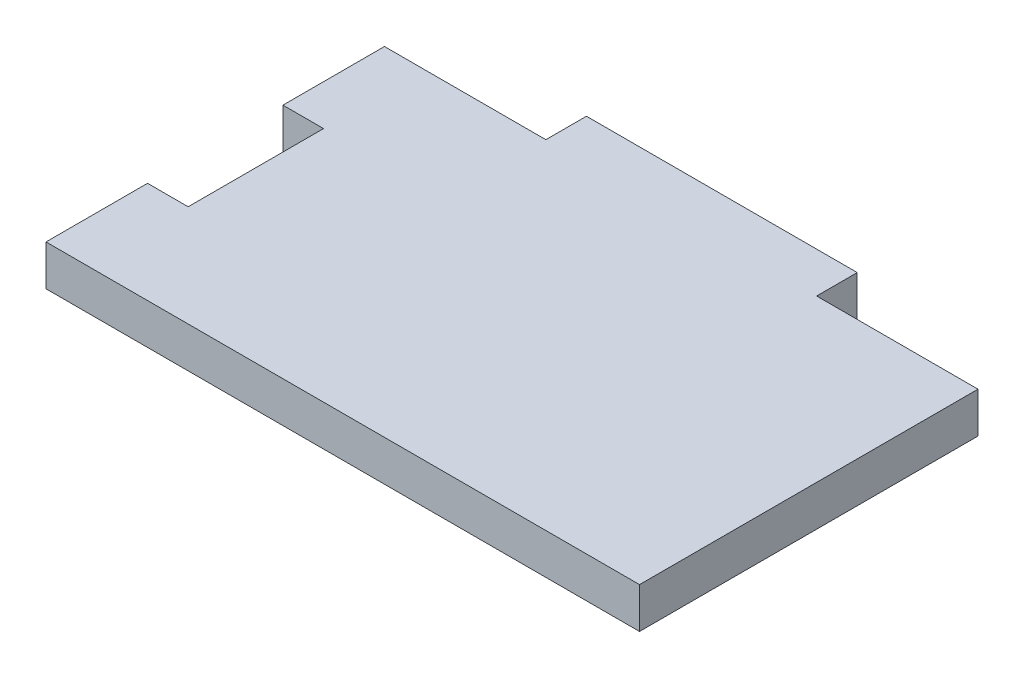
SolidWorks part; units mm, degrees
ref_plane "Front Plane" through (0, 0, 0) normal (0, 0, 1) x (1, 0, 0)
ref_plane "Top Plane" through (0, 0, 0) normal (0, 1, 0) x (1, 0, 0)
ref_plane "Right Plane" through (0, 0, 0) normal (1, 0, 0) x (0, 0, -1)
sketch "Sketch1" plane through (0, 0, 0) normal (0, 0, 1) x (1, 0, 0)
  line L1 (-54.8559, -41.0083) -> (32.8193, -41.0083)
  line L2 (-54.8559, -41.0083) -> (-54.8559, -35.0083)
  line L3 (-54.8559, -35.0083) -> (32.8193, -35.0083)
  line L4 (32.8193, -41.0083) -> (32.8193, -35.0083)
  line L5 (-31.0183, -35.0083) -> (-31.0183, -41.0083)
  line L6 (8.9817, -35.0083) -> (8.9817, -41.0083)
  point P5 (0, 0)
  point P6 (0, 0)
  point P15 (0, 0)
  point P16 (0, 0)
  dimension "D1" = 87.6752
  dimension "D2" = 6
extrude "Boss-Extrude1" add sketch "Sketch1" along normal blind 50 contours L5 L3 L2 L1 | L6 L3 L5 L1 | L3 L6 L1 L4 region at (-42.9371, -38.0083, 0) region at (-11.0183, -38.0083, 0) region at (20.9005, -38.0083, 0)
extrude "Boss-Extrude2" add sketch "Sketch1<3>" against normal blind 6 contours L6 L3 L5 L1 region at (-11.0183, -38.0083, 0)
sketch "Sketch1<3>" plane through (0, 0, 0) normal (0, 0, 1) x (1, 0, 0) same geometry as "Sketch1"
sketch "Sketch2" plane through (0, -35.0083, 0) normal (0, 1, 0) x (1, 0, 0)
  line L0 (-54.8559, -50) -> (-54.8559, 0) construction
  line L1 (-54.8559, -15) -> (-48.8559, -15)
  line L2 (-54.8559, -15) -> (-54.8559, -35)
  line L3 (-54.8559, -35) -> (-48.8559, -35)
  line L4 (-48.8559, -15) -> (-48.8559, -35)
  point P6 (-54.8559, -25)
  point P7 (-48.8559, -25)
  dimension "D1" = 20
  dimension "D2" = 6
extrude "Cut-Extrude1" cut sketch "Sketch2" against normal blind 6
